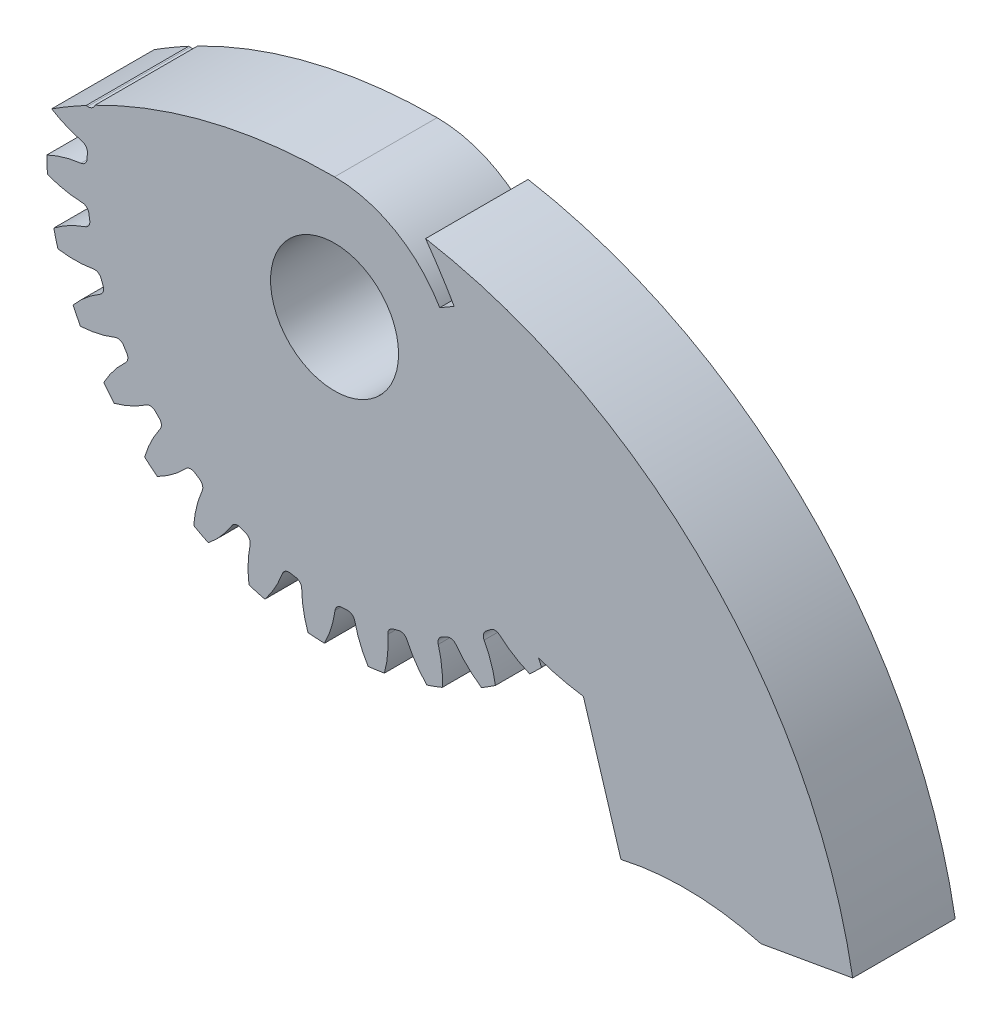
SolidWorks part; units mm, degrees
material "ABS"
ref_plane "Front" through (0, 0, 0) normal (0, 0, 1) x (1, 0, 0)
ref_plane "Top" through (0, 0, 0) normal (0, 1, 0) x (1, 0, 0)
ref_plane "Right" through (0, 0, 0) normal (1, 0, 0) x (0, 0, -1)
sketch "Sketch3" plane through (0, 0, 0) normal (0, 0, 1) x (1, 0, 0)
  circle A0 centre (0, 0) radius 40.64
  dimension "od" = 81.28
extrude "gearBody" add sketch "Sketch3" along normal blind 9.652
sketch "Sketch2" plane through (0, 0, 0) normal (0, 0, 1) x (1, 0, 0)
  line L0 (0, 0) -> (34.0786, 14.1158) construction
  line L1 (45.4751, -11.4855) -> (0, 0) construction
  line L2 (0, 0) -> (36.3143, 0) construction
  line L3 (38.0972, -0.458) -> (37.8451, -4.4001) construction
  line L5 (37.9712, -2.4291) -> (0, 0) construction
  line L7 (0, 0) -> (36.8864, 0) construction
  arc A0 (36.879, -0.7403) -> (36.6727, -3.9649) centre (0, 0) ccw construction
  arc A1 (40.637, 0.4947) -> (40.2427, -5.6687) centre (0, 0) ccw construction
  arc A2 (38.0972, -0.458) -> (37.8451, -4.4001) centre (0, 0) ccw construction
  arc A3 (34.9015, -2.6404) -> (34.9534, -1.8283) centre (0, 0) ccw
  arc A4 (45.4751, -11.4855) -> (35.6466, -3.6712) centre (32.0022, -18.3431) ccw
  arc A5 (45.4751, -11.4855) -> (46.5679, 5.5974) centre (0, 0) ccw
  arc A6 (46.5679, 5.5974) -> (35.8238, -0.9008) centre (34.0786, 14.1158) cw
  arc A7 (34.9534, -1.8283) -> (35.8238, -0.9008) centre (35.9376, -1.8798) cw
  arc A8 (35.6466, -3.6712) -> (34.9015, -2.6404) centre (35.8842, -2.7147) cw
  point P6 (46.5679, 5.5974)
  point P22 (45.4751, -11.4855)
  dimension "baseDia" = 73.7729
  dimension "od" = 81.28
  dimension "pd" = 76.2
  dimension "rd" = 70.0024
  dimension "rFillet" = 0.9855
  dimension "pointX" = 46.5679
  dimension "pointY" = 5.5974
  dimension "CTT" = 3.9421
  dimension "flankCenterAngle" = 22.5
extrude "toothCut" cut sketch "Sketch2" along normal through all
pattern_circular "CirPattern1" count 30 over 360 about axis through (0, 0, 9.652) along (0, 0, -1) of "toothCut"
scale "Scale1" scale about centroid uniform scaling no x scale factor 0.666667 y scale factor 0.666667 z scale factor 1
sketch "hub1Dia" plane through (0, 0, 0) normal (0, 0, -1) x (-1, 0, 0)
  circle A0 centre (0, 0) radius 12.7
  dimension "hub1Dia" = 25.4
sketch "hub2Dia" plane through (0, 0, 9.652) normal (0, 0, 1) x (1, 0, 0)
  circle A0 centre (0, 0) radius 12.7
  dimension "hub2dia" = 25.4
sketch "boreDia" plane through (0, 0, 0) normal (0, 0, 1) x (1, 0, 0)
  circle A0 centre (0, 0) radius 6.0255
  dimension "boreDia" = 12.051
extrude "bore" cut sketch "boreDia" against normal mid plane 25400
sketch "Sketch4" plane through (0, 0, 9.652) normal (0, 0, 1) x (1, 0, 0)
  circle A0 centre (0, -38.1) radius 49.53
  arc A2 (-27.1267, 3.3411) -> (27.1267, 3.3411) centre (0, 0) cw
  dimension "D1" = 99.06
  dimension "D2" = 38.1
extrude "Cut-Extrude1" cut sketch "Sketch4" against normal through all contours A0 region at (0, 16.3548, 9.652)
sketch "Sketch5" plane through (0, 0, 9.652) normal (0, 0, 1) x (1, 0, 0)
  line L0 (0, -38.1) -> (49.53, -38.1) construction
  line L1 (0, 0) -> (0, -38.1) construction
  line L2 (0, -38.1) -> (-24.765, 4.7942) construction
  line L3 (0, -38.1) -> (42.8942, -62.865) construction
  line L4 (23.4248, -19.2156) -> (26.9592, -30.742)
  line L6 (48.7775, -29.4992) -> (0, -38.1) construction
  line L7 (40.1449, -31.0214) -> (48.7775, -29.4992)
  circle A0 centre (0, -38.1) radius 49.53 construction
  circle A2 centre (0, -38.1) radius 14.3933 construction
  circle A3 centre (32.9956, -57.15) radius 27.0891 construction
  arc A4 (26.9592, -30.742) -> (40.1449, -31.0214) centre (32.9956, -57.15) cw
  arc A5 (48.7775, -29.4992) -> (8.0038, 10.779) centre (0, -38.1) ccw
  arc A6 (24.6567, 4.8566) -> (-22.5513, 5.9983) centre (0, -38.1) ccw construction
  spline S0 degree 2 poles (8.0038, 10.779) (4.7007, -16.4877) (23.4248, -19.2156) knots 0 0 0 1 1 1
  dimension "D2" = 28.7867
  dimension "D4" = 54.1782
  dimension "D1" = 120
  dimension "D3" = 120
  dimension "D5" = 38.1
  dimension "D6" = 80
extrude "Boss-Extrude1" add sketch "Sketch5" against normal up to surface (9.652 mm away) up to face at (6.0255, 0, 0)
sketch "Sketch6" plane through (0, 0, 9.652) normal (0, 0, 1) x (1, 0, 0)
  line L0 (0, 0) -> (-32.9956, -19.05) construction
  line L1 (0, 0) -> (0, -38.1) construction
  line L2 (-32.9956, -19.05) -> (0, 0) construction
  line L3 (11.2625, 6.5024) -> (9.8987, 5.715)
  circle A0 centre (-32.9956, -19.05) radius 49.53 construction
  circle A1 centre (-32.9956, -19.05) radius 51.1048 construction
  arc A3 (48.7775, -29.4992) -> (-22.5513, 5.9983) centre (0, -38.1) ccw construction
  arc A4 (11.2625, 6.5024) -> (8.5694, 10.6831) centre (-32.9956, -19.05) ccw
  circle A5 centre (0, -38.1) radius 49.53 construction
  arc A6 (8.5694, 10.6831) -> (0, 11.43) centre (0, -38.1) ccw
  arc A7 (9.8987, 5.715) -> (0, 11.43) centre (0, 0) ccw
  dimension "D1" = 99.06
  dimension "D4" = 102.2096
  dimension "D2" = 60
  dimension "D3" = 38.1
extrude "Body Tube Cut Out" cut sketch "Sketch6" against normal through all
equation "\"Aft_Section_Length\" = 32in"
equation "\"Mid_Coupler_Length\" = 12in"
equation "\"AB_Coupler_OD_Length\"= 1in"
equation "\"AB_Coupling_Section_Length\"= 0.375in"
equation "\"AB_Coupler_Length\"= \"AB_Coupler_OD_Length\" + \"AB_Coupling_Section_Length\" * 2"
equation "\"Cutout_Angle\" = 60"
equation "\"AB_Paddle_Height\" = 0.375in"
equation "\"AB_Coupler_Num_Screws\"= 4"
equation "\"Num_Cutouts\" = 4"
equation "\"AB_Coupler_OD\"= 4.024in"
equation "\"AB_Coupler_ID\"= 3.7in"
equation "\"AB_Coupler_Surface_Diameter\"= 3.899in"
equation "\"AB_Coupling_Screw_Diameter\"= 4.5mm"
equation "\"AB_Central_Bushing_Length\" = 0.75in"
equation "\"Lead_Screw_Dist\" = 2in"
equation "\"Lead_Screw_Diam\" = 0.375in"
equation "\"Lead_Screw_Length\" = \"Mid_Coupler_Length\" + 2*0.375in + 2*0.5in"
equation "\"Paddle_Pin_Offset\" = 0.25in"
equation "\"Paddle_Pin_Radius\" = 2.25*2/3in"
equation "\"Fwd_BKHD_From_Top\" = 18in"
equation "\"D1@Sketch4\"=\"Body_Tube_ID\""
equation "\"D2@Sketch4\"=\"Paddle_Pin_Radius\""
equation "\"Motor_OD\" = 54.4mm"
equation "\"Paddle_Gear_OD\" = 3.2in"
equation "\"Drive_Gear_OD\" = 1.7*2/3in"
equation "\"Fin_Thickness\" = 0.118in"
equation "\"DB9_Hole_Dist\" = 25mm"
equation "\"Motor_Length\" = 401mm"
equation "\"Body_Tube_OD\"= 4.024in"
equation "\"Body_Tube_ID\"= 3.90in"
equation "\"Coupler_OD\" = 3.899in"
equation "\"Coupler_ID\" = 3.755in"
equation "\"Fwd_Section_Length\" = 20in"
equation "\"Mid_Section_Length\" = 4in"
equation "\"Aft_Upper_Tube_Length\" = 10in"
equation "\"Aft_Lower_Tube_Length\" = 18in"
equation "\"Nosecone_Coupler_Length\" = 5in"
equation "\"Avionics_Bulkhead_Thickness\" = 0.25in"
equation "\"Avionics_Bulkhead_Lip\" = 0.125in"
equation "\"Avionics_Board_Length\" = \"Mid_Coupler_Length\" - 2*\"Avionics_Bulkhead_Lip\""
equation "\"Lead_Screw_Hole_Diam\" = 0.386in"
equation "\"Centering_Ring_Cutout_Dia\"= 1in"
equation "\"Airbrakes_Wire_Hole_Dist\" = 1.1*2/3in"
equation "\"Airbrakes_Wire_Hole_Dia\" = 0.25in"
equation "\"DB9_Relief_Width\" = 0.47in"
equation "\"DB9_Relief_Hole_Offset\" = 0.09in"
equation "\"Servo_Gear_Offset\" = 0.5in"
equation "\"D2@Sketch5\"=\"Drive_Gear_OD\""
equation "\"D5@Sketch5\"=\"Paddle_Pin_Radius\""
equation "\"D1@Sketch6\"=\"Body_Tube_ID\""
equation "\"D2@Sketch6\"=60"
equation "\"D3@Sketch6\"=\"Paddle_Pin_Radius\""
equation "\"D4@Sketch6\"=\"Body_Tube_OD\""
equation "\"Airbrake_Shaft_Diameter\"= 12.051mm"
equation "\"boreDia@boreDia\"=\"Airbrake_Shaft_Diameter\""
